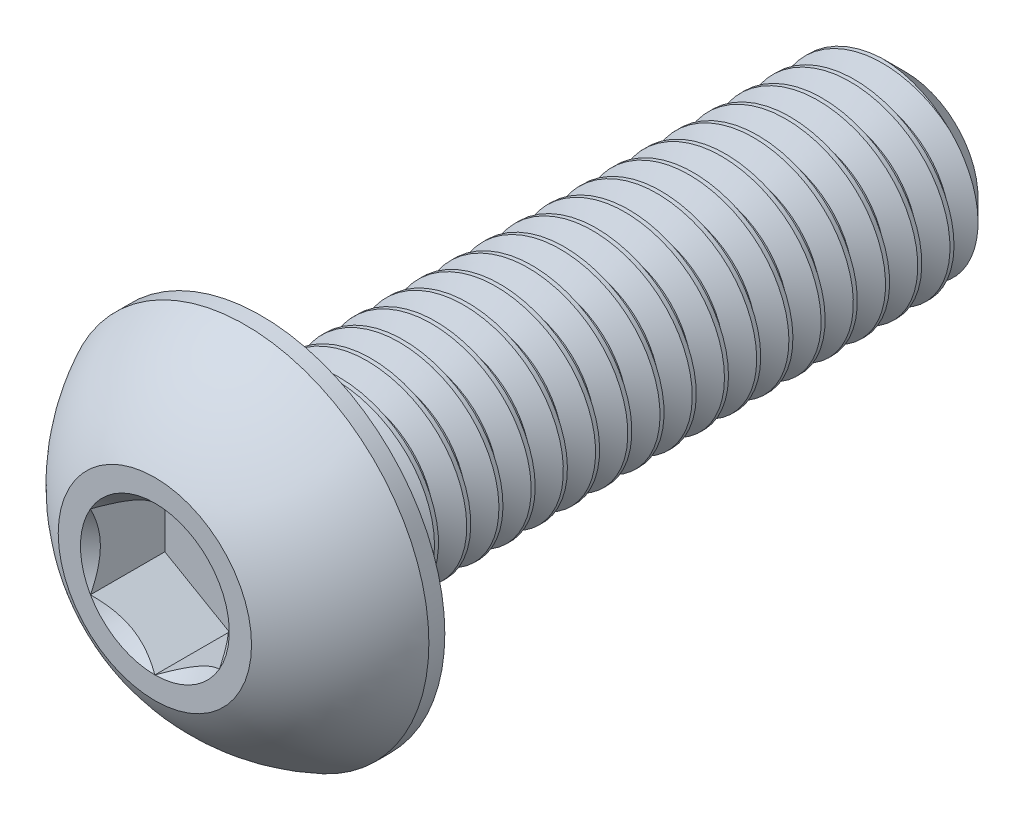
SolidWorks part; units mm, degrees
note: '?' marks a value the reader was unsure of.
ref_plane "Front" through (0, 0, 0) normal (0, 0, 1) x (1, 0, 0)
ref_plane "Top" through (0, 0, 0) normal (0, 1, 0) x (1, 0, 0)
ref_plane "Right" through (0, 0, 0) normal (1, 0, 0) x (0, 0, -1)
sketch "Sketch1" plane through (0, 0, 0) normal (1, 0, 0) x (0, 0, -1)
  line L2 (1.65, 1.5) -> (11.65, 1.5)
  line L3 (11.65, 1.5) -> (11.65, 0)
  line L4 (11.65, 0) -> (1.65, 0)
  line L6 (1.4025, 2.85) -> (1.65, 2.85) construction
  line L7 (11.65, 1.5) -> (11.65, -1.5) construction
  line L8 (0, 0) -> (1.65, 0) construction
  line L9 (1.65, 2.85) -> (1.65, -2.85) construction
  line L11 (1.65, 1.5) -> (1.65, 0)
  line L13 (0, 1) -> (0, -1) construction
  line L14 (0, 1) -> (0, 1.5) construction
  arc A3 (0, 1.5) -> (1.4025, 2.85) centre (2.7948, 0) cw construction
  dimension "D1" = 0.2475
revolve "Revolve1" add sketch "Sketch1" angle 360 mid plane about L4
sketch "Sketch3" plane through (0, 0, -11.65) normal (0, 0, -1) x (-1, 0, 0)
  circle A0 centre (0, 0) radius 1.5
curve "Helix/Spiral1" pitch 0.5 height 10.5 turns 21
chamfer "Chamfer1" distance 0.375 angle 45 1 edges at (0, 1.5, -11.65)
sketch "Sketch7" plane through (0, 0, 0) normal (1, 0, 0) x (0, 0, -1)
  line L6 (1.4025, 2.85) -> (1.65, 2.85) construction
  line L8 (0, 0) -> (1.65, 0) construction
  line L11 (1.65, 2.85) -> (1.65, -2.85) construction
  line L12 (1.4025, 2.85) -> (1.65, 2.85)
  line L13 (0, 0) -> (1.65, 0)
  line L14 (0, 1) -> (0, -1) construction
  line L15 (1.65, 2.85) -> (1.65, 0)
  line L16 (0, 1.5) -> (0, 0)
  arc A2 (1.4025, 2.85) -> (0, 1.5) centre (2.7948, 0) ccw construction
  arc A3 (1.4025, 2.85) -> (0, 1.5) centre (2.7948, 0) ccw
revolve "Revolve2" add sketch "Sketch7" angle 360 mid plane about L13
sketch "Sketch5" plane through (0, 0, 0) normal (0, 0, 1) x (1, 0, 0)
  line L1 (1, -0.5774) -> (1, 0.5774)
  line L2 (1, 0.5774) -> (0, 1.1547)
  line L3 (0, 1.1547) -> (-1, 0.5774)
  line L4 (-1, 0.5774) -> (-1, -0.5774)
  line L5 (-1, -0.5774) -> (0, -1.1547)
  line L6 (0, -1.1547) -> (1, -0.5774)
  circle A0 centre (0, 0) radius 1 construction
extrude "Cut-Extrude2" cut sketch "Sketch5" against normal blind 1.155
sketch "Sketch6" plane through (0, 0, 0) normal (0, 0, 1) x (1, 0, 0)
  circle A0 centre (0, 0) radius 1.1547
extrude "Cut-Extrude3" cut sketch "Sketch6" against normal blind 1.155 draft 45
sketch "Sketch2" plane through (0, 0, 0) normal (1, 0, 0) x (0, 0, -1)
  line L0 (11.275, 1.5) -> (11.7125, 1.5)
  line L1 (11.7125, 1.5) -> (11.525, 1.1752)
  line L2 (11.525, 1.1752) -> (11.4625, 1.1752)
  line L3 (11.4625, 1.1752) -> (11.275, 1.5)
  line L4 (11.3688, 1.3376) -> (11.6188, 1.3376) construction
  dimension "D1" = 60
  dimension "D2" = 0.0625
  dimension "D3" = 0.25
sweep "Cut-Sweep1" cut profiles "Sketch2" path "Helix/Spiral1"
sketch "Sketch10" plane through (0, 0, 0) normal (1, 0, 0) x (0, 0, -1)
  line L0 (11.65, 1.5) -> (11.65, -1.5) construction
  point P0 (10.9, -1.5)
  dimension "D1" = 0.75
ref_axis "Center Axis 1" through (0, 0, -8.1113) along (0, 0, 1)?
ref_plane "Contact Plane 1" through (0, 0, -1.65) normal (0, 0, -1) x (-1, 0, 0)
ref_plane "Contact Plane 2" through (0, 0, 0) normal (0, 0, 1) x (1, 0, 0)
equation "\"D3@Helix/Spiral1\" = \"Lg@Sketch1\" + \"D4@Helix/Spiral1\""
equation "\"D2@Sketch2\" = \"D4@Helix/Spiral1\" * .125"
equation "\"D3@Sketch2\" = \"D4@Helix/Spiral1\" * .5"
equation "\"D1@Chamfer1\" = \"D4@Helix/Spiral1\" * .75"
equation "\"D1@Cut-Extrude2\" = \"Head Ht@Sketch1\" * .7"
equation "\"D1@Sketch1\" = \"Head Ht@Sketch1\" * .15"
equation "\"D1@Sketch10\" = \"D4@Helix/Spiral1\" * 1.5"
equation "\"D1@Cut-Extrude3\" = \"D1@Cut-Extrude2\""
